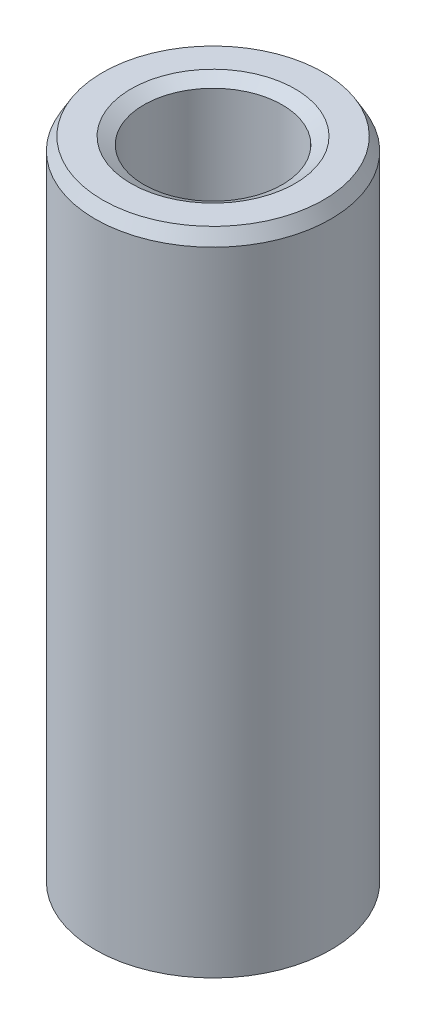
SolidWorks part; units mm, degrees
ref_plane "Front Plane" through (0, 0, 0) normal (0, 0, 1) x (1, 0, 0)
ref_plane "Top Plane" through (0, 0, 0) normal (0, 1, 0) x (1, 0, 0)
ref_plane "Right Plane" through (0, 0, 0) normal (1, 0, 0) x (0, 0, -1)
sketch "Sketch1" plane through (0, 0, 0) normal (0, 1, 0) x (1, 0, 0)
  circle A0 centre (0, 0) radius 22.5
  dimension "SLEEVE_OD" = 45
extrude "Boss-Extrude1" add sketch "Sketch1" along normal blind 124.6539
sketch "Sketch2" plane through (0, 0, 0) normal (0, 1, 0) x (1, 0, 0)
  circle A0 centre (0, 0) radius 13.2084
  dimension "BORE_D" = 26.4169
extrude "Cut-Extrude1" cut sketch "Sketch2" along normal through all
chamfer "Chamfer1" distance 2.4501 angle 30 4 edges at (0, 124.6539, 13.2084) (0, 0, 13.2084) (0, 0, 22.5) (0, 124.6539, 22.5) first distance on face at (0, 124.6539, 13.2084) first distance on face at (0, 0, 13.2084) first distance on face at (0, 124.6539, 22.5)
